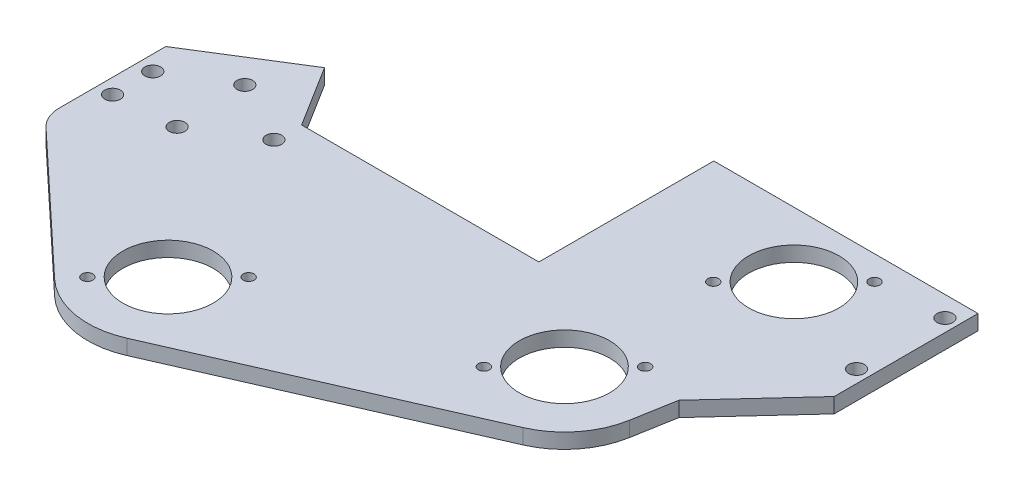
SolidWorks part; units mm, degrees
ref_plane "Front Plane" through (0, 0, 0) normal (0, 0, 1) x (1, 0, 0)
ref_plane "Top Plane" through (0, 0, 0) normal (0, 1, 0) x (1, 0, 0)
ref_plane "Right Plane" through (0, 0, 0) normal (1, 0, 0) x (0, 0, -1)
sketch "Sketch1" plane through (0, 0, 0) normal (0, 1, 0) x (1, 0, 0)
  line L1 (-62.0382, -79.8833) -> (25.1671, -41.6958)
  line L5 (39.9402, -22.8907) -> (42.2751, -9.5867)
  line L6 (42.2751, -9.5867) -> (65.831, 16.0128)
  line L12 (-135.7544, -31.9237) -> (-135.7544, 6.1763)
  line L16 (-92.7762, 6.1643) -> (-17.7344, 6.1643)
  line L17 (-135.7544, -31.9237) -> (-89.5888, -75.1562)
  line L19 (65.831, 61.4936) -> (-17.7344, 61.4936)
  line L20 (65.831, 16.0128) -> (65.831, 61.4936)
  line L22 (-17.7344, 61.4936) -> (-17.7344, 6.1643)
  line L23 (-135.7544, 6.1763) -> (-104.8504, 25.4872)
  line L24 (-205.1725, 186.0361) -> (-71.6498, -27.6449) construction
  line L25 (-104.8504, 25.4872) -> (-92.7762, 6.1643)
  line L26 (-72.2583, -56.6285) -> (15.031, -18.5085) construction
  line L27 (-72.2269, -82.0164) -> (109.3231, -82.0164) construction
  line L28 (15.0167, -18.5164) -> (15.0167, -82.0164) construction
  circle A0 centre (28.0466, 41.0458) radius 14.29
  circle A1 centre (15.031, -18.5085) radius 14.29
  circle A2 centre (-72.2583, -56.6285) radius 14.29
  arc A4 (39.9402, -22.8907) -> (25.1671, -41.6958) centre (15.0167, -18.5164) cw
  arc A6 (-62.0382, -79.8833) -> (-89.5888, -75.1562) centre (-72.2269, -56.6164) cw
  circle A7 centre (15.031, -18.5085) radius 25.4 construction
  circle A8 centre (-72.2583, -56.6285) radius 25.4 construction
  circle A9 centre (-28.6137, -37.5685) radius 22.225 construction
  circle A10 centre (28.0466, 41.0458) radius 30.48 construction
  circle A11 centre (15.031, -18.5085) radius 30.48 construction
  point P11 (-62.0382, -79.8833)
  point P34 (15.0167, -18.5164)
  point P35 (28.0466, 41.0458)
  dimension "D2" = 50.8
  dimension "D3" = 50.8
  dimension "D4" = 44.45
  dimension "D5" = 63.5
  dimension "D7" = 60.96
  dimension "D8" = 60.96
  dimension "D1" = 140.0048
  dimension "D6" = 95.25
  dimension "D9" = 50.8
  dimension "D10" = 143.51
extrude "Boss-Extrude1" add sketch "Sketch1" along normal blind 4.7625
fillet "Fillet1" radius 10 1 edges at (-135.7544, 2.3813, 31.9237)
hole_wizard "#10 Clearance Hole1" positions "Sketch2" profile "Sketch3" hole size "#10" standard "ANSI Inch" end condition through all
sketch "Sketch2" plane through (0, 4.7625, 0) normal (0, 1, 0) x (1, 0, 0)
  point P0 (61.8305, 55.0158)
  point P3 (61.8305, 27.0758)
  point P7 (-130.9919, -2.7257)
  point P10 (-130.9919, -15.4257)
sketch "Sketch3" plane through (61.8305, 4.7625, -55.0158) normal (1, 0, 0) x (0, 0, 1)
  line L0 (0, 0) -> (0, 4.7625)
  line L1 (0, 4.7625) -> (2.4892, 4.7625)
  line L2 (2.4892, 4.7625) -> (2.4892, 0)
  line L5 (2.4892, 0) -> (0, 0)
  line L11 (0, -6.35) -> (0, 107.95) construction
  dimension "Thru Hole Dia." = 4.9784
  dimension "Thru Hole Depth" = 4.7625
sketch "Sketch4" plane through (0, 4.7625, 0) normal (0, 1, 0) x (1, 0, 0)
  line L0 (-72.2583, -56.6285) -> (-102.5432, -8.1625) construction
  line L1 (-102.5432, -8.1625) -> (-93.1193, -2.2738) construction
  line L2 (-102.5432, -8.1625) -> (-111.9672, -14.0512) construction
  line L3 (-102.5432, -8.1625) -> (-112.7324, 8.1436) construction
  line L4 (-102.5432, -8.1625) -> (-186.6679, 126.4651) construction
  line L5 (65.831, 41.0458) -> (65.831, 28.3458) construction
  dimension "D1" = 57.15
  dimension "D2" = 22.225
  dimension "D3" = 32
hole_wizard "#10 Clearance Hole2" positions "Sketch5" profile "Sketch6" hole size "#10" standard "ANSI Inch" end condition through all
sketch "Sketch5" plane through (0, 4.7625, 0) normal (0, 1, 0) x (1, 0, 0)
  point P0 (-111.9672, -14.0512)
  point P3 (-93.1193, -2.2738)
  point P7 (-112.7324, 8.1436)
sketch "Sketch6" plane through (-111.9672, 4.7625, 14.0512) normal (1, 0, 0) x (0, 0, 1)
  line L0 (0, 0) -> (0, 4.7625)
  line L1 (0, 4.7625) -> (2.4892, 4.7625)
  line L2 (2.4892, 4.7625) -> (2.4892, 0)
  line L5 (2.4892, 0) -> (0, 0)
  line L11 (0, -6.35) -> (0, 107.95) construction
  dimension "Thru Hole Dia." = 4.9784
  dimension "Thru Hole Depth" = 4.7625
sketch "Sketch7" plane through (0, 4.7625, 0) normal (0, 1, 0) x (1, 0, 0)
  line L0 (-85.0103, -69.3804) -> (-59.5064, -43.8765) construction
  line L1 (2.279, -31.2604) -> (27.783, -5.7565) construction
  line L3 (15.2946, 28.2939) -> (40.7985, 53.7978) construction
  point P7 (-72.2583, -56.6285)
  point P11 (15.031, -18.5085)
  point P13 (28.0466, 41.0458)
hole_wizard "Tap Drill for #8-32 Tap1" positions "Sketch8" profile "Sketch9" hole size "#8-32" standard "ANSI Inch" end condition through all
sketch "Sketch8" plane through (0, 4.7625, 0) normal (0, 1, 0) x (1, 0, 0)
  point P0 (-59.5064, -43.8765)
  point P3 (-85.0103, -69.3804)
  point P6 (2.279, -31.2604)
  point P9 (27.783, -5.7565)
  point P12 (15.2946, 28.2939)
  point P15 (40.7985, 53.7978)
sketch "Sketch9" plane through (-59.5064, 4.7625, 43.8765) normal (1, 0, 0) x (0, 0, 1)
  line L0 (0, 0) -> (0, 4.7625)
  line L1 (0, 4.7625) -> (1.7272, 4.7625)
  line L2 (1.7272, 4.7625) -> (1.7272, 0)
  line L5 (1.7272, 0) -> (0, 0)
  line L11 (0, -6.35) -> (0, 107.95) construction
  dimension "Thru Hole Dia." = 3.4544
  dimension "Thru Hole Depth" = 4.7625
